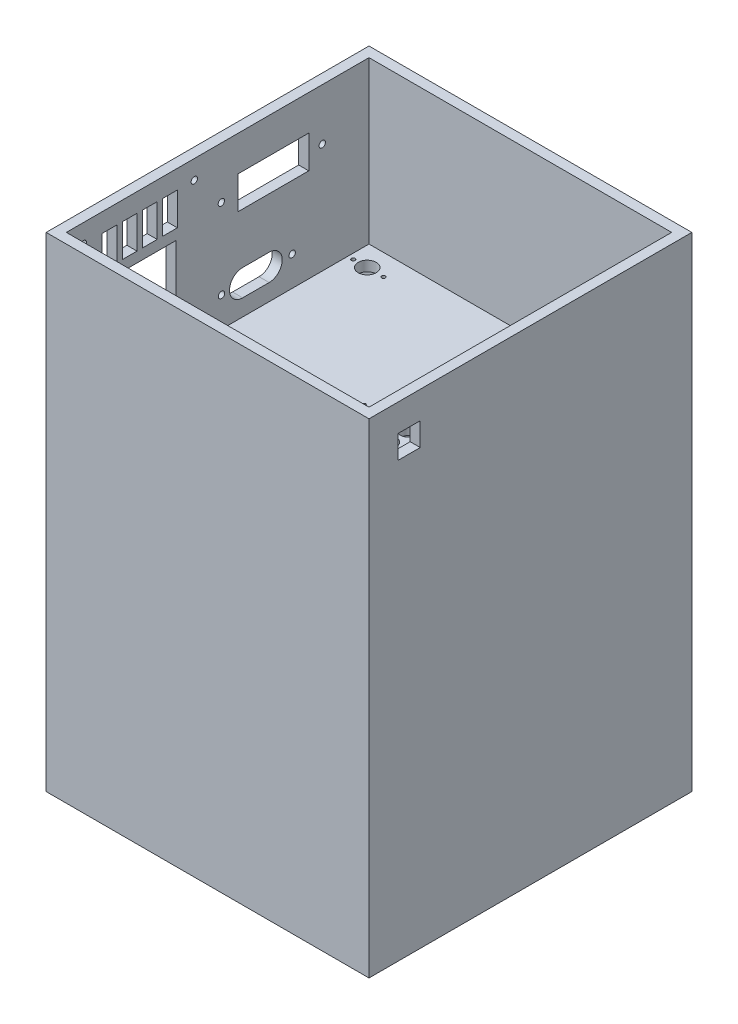
SolidWorks part; units mm, degrees
ref_plane "Front Plane" through (0, 0, 0) normal (0, 0, 1) x (1, 0, 0)
ref_plane "Top Plane" through (0, 0, 0) normal (0, 1, 0) x (1, 0, 0)
ref_plane "Right Plane" through (0, 0, 0) normal (1, 0, 0) x (0, 0, -1)
sketch "Sketch1" plane through (0, 0, 0) normal (0, 0, 1) x (1, 0, 0)
  line L1 (-101.6, -101.6) -> (101.6, -101.6)
  line L2 (-101.6, -101.6) -> (-101.6, 101.6)
  line L3 (-101.6, 101.6) -> (101.6, 101.6)
  line L4 (101.6, -101.6) -> (101.6, 101.6)
  line L5 (-101.6, -101.6) -> (101.6, 101.6) construction
  line L6 (-101.6, 101.6) -> (101.6, -101.6) construction
  line L11 (-94.7622, -94.7622) -> (94.7622, 94.7622) construction
  line L12 (-94.7622, 94.7622) -> (94.7622, -94.7622) construction
  point P0 (0, 0)
  point P6 (0, 0)
  dimension "D1" = 203.2
  dimension "D2" = 203.2
extrude "Boss-Extrude1" add sketch "Sketch1" along normal blind 203.2
sketch "Sketch2" plane through (-101.6, 0, 0) normal (-1, 0, 0) x (0, 0, 1)
  point P10 (101.6, 0)
shell "Shell1" thickness 6.35 removed face at (-101.6, 0, 101.6)
sketch "Sketch4" plane through (0, 101.6, 0) normal (0, 1, 0) x (1, 0, 0)
  line L0 (101.6, -203.2) -> (101.6, 0) construction
  line L1 (-101.6, 0) -> (101.6, 0)
  line L2 (-101.6, 0) -> (-101.6, -203.2)
  line L3 (-101.6, -203.2) -> (101.6, -203.2)
  line L4 (101.6, 0) -> (101.6, -203.2)
  line L5 (-101.6, 0) -> (101.6, -203.2) construction
  line L6 (-101.6, -203.2) -> (101.6, 0) construction
  line L7 (101.6, 0) -> (-101.6, 0) construction
  point P0 (0, -101.6)
  dimension "D1" = 203.2
  dimension "D2" = 203.2
  dimension "D3" = 101.6
  dimension "D4" = 101.6
extrude "Boss-Extrude2" add sketch "Sketch4" along normal blind 101.6
shell "Shell2" thickness 6.35 removed face at (0, 203.2, 101.6)
sketch "Sketch5" plane through (-101.6, 0, 0) normal (-1, 0, 0) x (0, 0, 1)
  line L0 (196.85, 101.6) -> (6.35, 101.6) construction
  line L1 (196.85, 101.6) -> (6.35, 101.6)
  line L2 (69.2241, 120.3089) -> (85.8961, 120.3089) construction
  line L3 (69.2241, 128.5657) -> (85.8961, 128.5657)
  line L4 (69.2241, 112.0522) -> (85.8961, 112.0522)
  line L5 (139.655, 191.3717) -> (148.8729, 170.7604) construction
  line L6 (44.262, 160.4548) -> (88.6863, 160.4548)
  line L7 (44.262, 160.4548) -> (44.262, 181.0661)
  line L8 (44.262, 181.0661) -> (88.6863, 181.0661)
  line L9 (88.6863, 160.4548) -> (88.6863, 181.0661)
  line L10 (44.262, 160.4548) -> (88.6863, 181.0661) construction
  line L11 (44.262, 181.0661) -> (88.6863, 160.4548) construction
  line L12 (126.955, 191.3717) -> (136.1729, 191.3717)
  line L13 (126.955, 191.3717) -> (126.955, 170.7604)
  line L14 (126.955, 170.7604) -> (136.1729, 170.7604)
  line L15 (136.1729, 191.3717) -> (136.1729, 170.7604)
  line L16 (126.955, 191.3717) -> (136.1729, 170.7604) construction
  line L17 (126.955, 170.7604) -> (136.1729, 191.3717) construction
  line L18 (139.655, 170.7604) -> (148.8729, 191.3717) construction
  line L19 (139.655, 191.3717) -> (139.655, 170.7604)
  line L20 (139.655, 191.3717) -> (148.8729, 191.3717)
  line L21 (148.8729, 191.3717) -> (148.8729, 170.7604)
  line L22 (139.655, 170.7604) -> (148.8729, 170.7604)
  line L23 (152.355, 191.3717) -> (161.5729, 170.7604) construction
  line L24 (152.355, 170.7604) -> (161.5729, 191.3717) construction
  line L25 (152.355, 191.3717) -> (152.355, 170.7604)
  line L26 (152.355, 191.3717) -> (161.5729, 191.3717)
  line L27 (161.5729, 191.3717) -> (161.5729, 170.7604)
  line L28 (152.355, 170.7604) -> (161.5729, 170.7604)
  line L29 (165.055, 191.3717) -> (174.2729, 170.7604) construction
  line L30 (165.055, 170.7604) -> (174.2729, 191.3717) construction
  line L31 (165.055, 191.3717) -> (165.055, 170.7604)
  line L32 (165.055, 191.3717) -> (174.2729, 191.3717)
  line L33 (174.2729, 191.3717) -> (174.2729, 170.7604)
  line L34 (165.055, 170.7604) -> (174.2729, 170.7604)
  line L36 (173.5773, 106.7848) -> (127.8397, 106.7848)
  line L37 (173.5773, 106.7848) -> (173.5773, 164.2797)
  line L38 (173.5773, 164.2797) -> (127.8397, 164.2797)
  line L39 (127.8397, 106.7848) -> (127.8397, 164.2797)
  line L40 (173.5773, 106.7848) -> (127.8397, 164.2797) construction
  line L41 (173.5773, 164.2797) -> (127.8397, 106.7848) construction
  arc A0 (69.2241, 128.5657) -> (69.2241, 112.0522) centre (69.2241, 120.3089) ccw
  arc A1 (85.8961, 112.0522) -> (85.8961, 128.5657) centre (85.8961, 120.3089) ccw
  circle A2 centre (54.7054, 120.3089) radius 2.0126
  circle A3 centre (99.1554, 120.3089) radius 2.0126
  circle A4 centre (35.7866, 170.7604) radius 2.0126
  circle A5 centre (99.2866, 170.7604) radius 2.0126
  circle A6 centre (116.2923, 191.3717) radius 2.0126
  circle A7 centre (186.1423, 191.3717) radius 2.0126
  circle A8 centre (186.1423, 108.8217) radius 2.0126
  circle A9 centre (116.2923, 108.8217) radius 2.0126
  point P4 (77.5601, 120.3089)
  point P9 (66.4742, 170.7604)
  point P14 (131.5639, 181.0661)
  point P19 (150.7085, 135.5323)
  point P20 (144.2639, 181.0661)
  point P25 (156.9639, 181.0661)
  point P30 (169.6639, 181.0661)
  dimension "D1" = 4
  dimension "D2" = 2
  dimension "D3" = 2
  dimension "D4" = 2
  dimension "D5" = 2
extrude "Cut-Extrude1" cut sketch "Sketch5" against normal up to surface (6.35 mm away) contours L37 L36 L39 L38 | L4 A1 L3 A0 | L7 L6 L9 L8 | L13 L12 L15 L14 | L19 L22 L21 L20 | L25 L28 L27 L26 | L31 L34 L33 L32 | A4 | A2 | A3 | A5 | A6 | A9 | A8 | A7
sketch "Sketch6" plane through (0, 101.6, 0) normal (0, 1, 0) x (1, 0, 0)
  line L0 (-0.7512, -80.4242) -> (9.4088, -70.2642) construction
  line L1 (-0.7512, -70.2642) -> (9.4088, -80.4242) construction
  line L2 (-95.25, -196.85) -> (95.25, -6.35) construction
  line L3 (95.25, -196.85) -> (-95.25, -6.35) construction
  line L5 (-9.2294, -94.3032) -> (-38.0172, -123.091)
  line L6 (-38.0172, -123.091) -> (-39.9596, -125.2811)
  line L8 (13.5313, -141.4537) -> (7.5423, -98.4298)
  circle A0 centre (-83.0171, -19.7153) radius 5.6849
  circle A1 centre (-91.8157, -19.7153) radius 1.1689
  circle A3 centre (-72.7657, -19.7153) radius 1.1689
  circle A4 centre (-0.7512, -80.4242) radius 3.4219
  circle A5 centre (9.4088, -80.4242) radius 3.4219
  circle A6 centre (9.4088, -70.2642) radius 3.4219
  circle A7 centre (-0.7512, -70.2642) radius 3.4219
  arc A8 (-39.9596, -125.2811) -> (13.5313, -141.4537) centre (4.3288, -75.3442) ccw
  circle A9 centre (18.775, -108.3076) radius 5.1018
  circle A11 centre (18.775, -95.6076) radius 5.1018
  arc A12 (-9.2294, -94.3032) -> (7.5423, -98.4298) centre (4.3288, -75.3442) ccw
  circle A13 centre (-55.964, -146.3132) radius 1.1689
  circle A14 centre (-55.964, -127.2632) radius 1.1689
  dimension "D1" = 2
  dimension "D2" = 2
  dimension "D3" = 2
  dimension "D4" = 2
  dimension "D5" = 2
extrude "Cut-Extrude2" cut sketch "Sketch6" against normal up to surface (6.35 mm away) up to face at (-3.175, 95.25, 101.6)
sketch "Sketch8" plane through (0, -101.6, 0) normal (0, -1, 0) x (1, 0, 0)
  circle A0 centre (18.775, 95.6076) radius 5.1018 construction
  circle A1 centre (18.775, 95.6076) radius 5.1018
  circle A2 centre (-89.4934, 190.6084) radius 3.3544
  circle A3 centre (88.3066, 190.6084) radius 3.3544
  circle A4 centre (88.3066, 12.8084) radius 3.3544
  circle A5 centre (-89.4934, 12.8084) radius 3.3544
  point P5 (-89.461, 191.5182)
  point P6 (0, 0)
  point P7 (0, 0)
  point P14 (0, 0)
  point P15 (-89.4934, 190.6084)
  dimension "D1" = 2
  dimension "D2" = 2
extrude "Cut-Extrude3" cut sketch "Sketch8" against normal up to surface (6.35 mm away) contours A3 | A2 | A1 | A4 | A5 region at (88.3066, -101.6, 190.6084) up to face at (-3.175, -95.25, 101.6)
sketch "Sketch9" plane through (101.6, 0, 0) normal (1, 0, 0) x (0, 0, -1)
  line L0 (-196.85, 101.6) -> (-6.35, 101.6) construction
  line L1 (-196.85, 101.6) -> (-6.35, 101.6)
  line L3 (-184.9664, 186.0509) -> (-170.9467, 186.0509)
  line L4 (-184.9664, 186.0509) -> (-184.9664, 171.4108)
  line L5 (-184.9664, 171.4108) -> (-170.9467, 171.4108)
  line L6 (-170.9467, 186.0509) -> (-170.9467, 171.4108)
  line L7 (-184.9664, 186.0509) -> (-170.9467, 171.4108) construction
  line L8 (-184.9664, 171.4108) -> (-170.9467, 186.0509) construction
  point P2 (-177.9566, 178.7309)
extrude "Cut-Extrude4" cut sketch "Sketch9" along direction (-1, 0, 0) on the side against the normal up to surface (6.35 mm away) contours L4 L3 L6 L5 up to face at (95.25, 152.4, 101.6)
